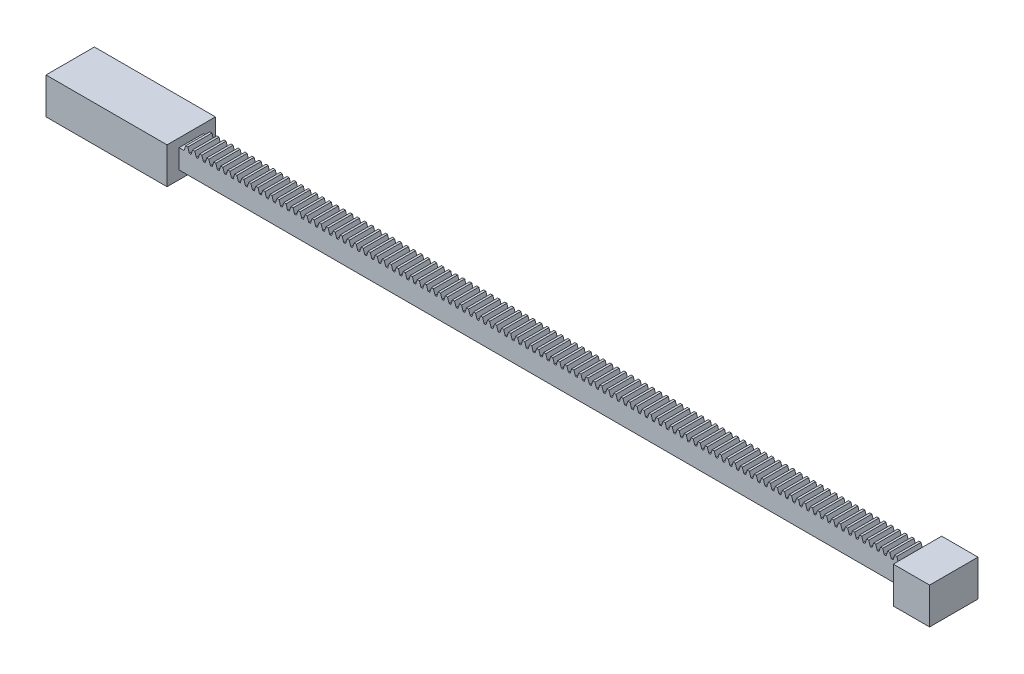
SolidWorks part; units mm, degrees
ref_plane "Front Plane" through (0, 0, 0) normal (0, 0, 1) x (1, 0, 0)
ref_plane "Top Plane" through (0, 0, 0) normal (0, 1, 0) x (1, 0, 0)
ref_plane "Right Plane" through (0, 0, 0) normal (1, 0, 0) x (0, 0, -1)
sketch "Sketch1" plane through (0, 0, 0) normal (0, 0, 1) x (1, 0, 0)
  line L0 (147.8394, 4) -> (148.4797, 6)
  line L1 (-150, 4) -> (150, 4)
  line L2 (-150, 4) -> (-150, -4)
  line L3 (-150, -4) -> (150, -4)
  line L4 (150, 4) -> (150, -4)
  line L5 (-150, 4) -> (150, -4) construction
  line L6 (-150, -4) -> (150, 4) construction
  line L7 (148.4797, 6) -> (149.3597, 6)
  line L8 (149.3597, 6) -> (150, 4)
  line L9 (144.9394, 4) -> (145.5797, 6)
  line L10 (145.5797, 6) -> (146.4597, 6)
  line L11 (146.4597, 6) -> (147.1, 4)
  line L12 (142.0394, 4) -> (142.6797, 6)
  line L13 (142.6797, 6) -> (143.5597, 6)
  line L14 (143.5597, 6) -> (144.2, 4)
  line L15 (139.1394, 4) -> (139.7797, 6)
  line L16 (139.7797, 6) -> (140.6597, 6)
  line L17 (140.6597, 6) -> (141.3, 4)
  line L18 (136.2394, 4) -> (136.8797, 6)
  line L19 (136.8797, 6) -> (137.7597, 6)
  line L20 (137.7597, 6) -> (138.4, 4)
  line L21 (133.3394, 4) -> (133.9797, 6)
  line L22 (133.9797, 6) -> (134.8597, 6)
  line L23 (134.8597, 6) -> (135.5, 4)
  line L24 (130.4394, 4) -> (131.0797, 6)
  line L25 (131.0797, 6) -> (131.9597, 6)
  line L26 (131.9597, 6) -> (132.6, 4)
  line L27 (127.5394, 4) -> (128.1797, 6)
  line L28 (128.1797, 6) -> (129.0597, 6)
  line L29 (129.0597, 6) -> (129.7, 4)
  line L30 (124.6394, 4) -> (125.2797, 6)
  line L31 (125.2797, 6) -> (126.1597, 6)
  line L32 (126.1597, 6) -> (126.8, 4)
  line L33 (121.7394, 4) -> (122.3797, 6)
  line L34 (122.3797, 6) -> (123.2597, 6)
  line L35 (123.2597, 6) -> (123.9, 4)
  line L36 (118.8394, 4) -> (119.4797, 6)
  line L37 (119.4797, 6) -> (120.3597, 6)
  line L38 (120.3597, 6) -> (121, 4)
  line L39 (115.9394, 4) -> (116.5797, 6)
  line L40 (116.5797, 6) -> (117.4597, 6)
  line L41 (117.4597, 6) -> (118.1, 4)
  line L42 (113.0394, 4) -> (113.6797, 6)
  line L43 (113.6797, 6) -> (114.5597, 6)
  line L44 (114.5597, 6) -> (115.2, 4)
  line L45 (110.1394, 4) -> (110.7797, 6)
  line L46 (110.7797, 6) -> (111.6597, 6)
  line L47 (111.6597, 6) -> (112.3, 4)
  line L48 (107.2394, 4) -> (107.8797, 6)
  line L49 (107.8797, 6) -> (108.7597, 6)
  line L50 (108.7597, 6) -> (109.4, 4)
  line L51 (104.3394, 4) -> (104.9797, 6)
  line L52 (104.9797, 6) -> (105.8597, 6)
  line L53 (105.8597, 6) -> (106.5, 4)
  line L54 (101.4394, 4) -> (102.0797, 6)
  line L55 (102.0797, 6) -> (102.9597, 6)
  line L56 (102.9597, 6) -> (103.6, 4)
  line L57 (98.5394, 4) -> (99.1797, 6)
  line L58 (99.1797, 6) -> (100.0597, 6)
  line L59 (100.0597, 6) -> (100.7, 4)
  line L60 (95.6394, 4) -> (96.2797, 6)
  line L61 (96.2797, 6) -> (97.1597, 6)
  line L62 (97.1597, 6) -> (97.8, 4)
  line L63 (92.7394, 4) -> (93.3797, 6)
  line L64 (93.3797, 6) -> (94.2597, 6)
  line L65 (94.2597, 6) -> (94.9, 4)
  line L66 (89.8394, 4) -> (90.4797, 6)
  line L67 (90.4797, 6) -> (91.3597, 6)
  line L68 (91.3597, 6) -> (92, 4)
  line L69 (86.9394, 4) -> (87.5797, 6)
  line L70 (87.5797, 6) -> (88.4597, 6)
  line L71 (88.4597, 6) -> (89.1, 4)
  line L72 (84.0394, 4) -> (84.6797, 6)
  line L73 (84.6797, 6) -> (85.5597, 6)
  line L74 (85.5597, 6) -> (86.2, 4)
  line L75 (81.1394, 4) -> (81.7797, 6)
  line L76 (81.7797, 6) -> (82.6597, 6)
  line L77 (82.6597, 6) -> (83.3, 4)
  line L78 (78.2394, 4) -> (78.8797, 6)
  line L79 (78.8797, 6) -> (79.7597, 6)
  line L80 (79.7597, 6) -> (80.4, 4)
  line L81 (75.3394, 4) -> (75.9797, 6)
  line L82 (75.9797, 6) -> (76.8597, 6)
  line L83 (76.8597, 6) -> (77.5, 4)
  line L84 (72.4394, 4) -> (73.0797, 6)
  line L85 (73.0797, 6) -> (73.9597, 6)
  line L86 (73.9597, 6) -> (74.6, 4)
  line L87 (69.5394, 4) -> (70.1797, 6)
  line L88 (70.1797, 6) -> (71.0597, 6)
  line L89 (71.0597, 6) -> (71.7, 4)
  line L90 (66.6394, 4) -> (67.2797, 6)
  line L91 (67.2797, 6) -> (68.1597, 6)
  line L92 (68.1597, 6) -> (68.8, 4)
  line L93 (63.7394, 4) -> (64.3797, 6)
  line L94 (64.3797, 6) -> (65.2597, 6)
  line L95 (65.2597, 6) -> (65.9, 4)
  line L96 (60.8394, 4) -> (61.4797, 6)
  line L97 (61.4797, 6) -> (62.3597, 6)
  line L98 (62.3597, 6) -> (63, 4)
  line L99 (57.9394, 4) -> (58.5797, 6)
  line L100 (58.5797, 6) -> (59.4597, 6)
  line L101 (59.4597, 6) -> (60.1, 4)
  line L102 (55.0394, 4) -> (55.6797, 6)
  line L103 (55.6797, 6) -> (56.5597, 6)
  line L104 (56.5597, 6) -> (57.2, 4)
  line L105 (52.1394, 4) -> (52.7797, 6)
  line L106 (52.7797, 6) -> (53.6597, 6)
  line L107 (53.6597, 6) -> (54.3, 4)
  line L108 (49.2394, 4) -> (49.8797, 6)
  line L109 (49.8797, 6) -> (50.7597, 6)
  line L110 (50.7597, 6) -> (51.4, 4)
  line L111 (46.3394, 4) -> (46.9797, 6)
  line L112 (46.9797, 6) -> (47.8597, 6)
  line L113 (47.8597, 6) -> (48.5, 4)
  line L114 (43.4394, 4) -> (44.0797, 6)
  line L115 (44.0797, 6) -> (44.9597, 6)
  line L116 (44.9597, 6) -> (45.6, 4)
  line L117 (40.5394, 4) -> (41.1797, 6)
  line L118 (41.1797, 6) -> (42.0597, 6)
  line L119 (42.0597, 6) -> (42.7, 4)
  line L120 (37.6394, 4) -> (38.2797, 6)
  line L121 (38.2797, 6) -> (39.1597, 6)
  line L122 (39.1597, 6) -> (39.8, 4)
  line L123 (34.7394, 4) -> (35.3797, 6)
  line L124 (35.3797, 6) -> (36.2597, 6)
  line L125 (36.2597, 6) -> (36.9, 4)
  line L126 (31.8394, 4) -> (32.4797, 6)
  line L127 (32.4797, 6) -> (33.3597, 6)
  line L128 (33.3597, 6) -> (34, 4)
  line L129 (28.9394, 4) -> (29.5797, 6)
  line L130 (29.5797, 6) -> (30.4597, 6)
  line L131 (30.4597, 6) -> (31.1, 4)
  line L132 (26.0394, 4) -> (26.6797, 6)
  line L133 (26.6797, 6) -> (27.5597, 6)
  line L134 (27.5597, 6) -> (28.2, 4)
  line L135 (23.1394, 4) -> (23.7797, 6)
  line L136 (23.7797, 6) -> (24.6597, 6)
  line L137 (24.6597, 6) -> (25.3, 4)
  line L138 (20.2394, 4) -> (20.8797, 6)
  line L139 (20.8797, 6) -> (21.7597, 6)
  line L140 (21.7597, 6) -> (22.4, 4)
  line L141 (17.3394, 4) -> (17.9797, 6)
  line L142 (17.9797, 6) -> (18.8597, 6)
  line L143 (18.8597, 6) -> (19.5, 4)
  line L144 (14.4394, 4) -> (15.0797, 6)
  line L145 (15.0797, 6) -> (15.9597, 6)
  line L146 (15.9597, 6) -> (16.6, 4)
  line L147 (11.5394, 4) -> (12.1797, 6)
  line L148 (12.1797, 6) -> (13.0597, 6)
  line L149 (13.0597, 6) -> (13.7, 4)
  line L150 (8.6394, 4) -> (9.2797, 6)
  line L151 (9.2797, 6) -> (10.1597, 6)
  line L152 (10.1597, 6) -> (10.8, 4)
  line L153 (5.7394, 4) -> (6.3797, 6)
  line L154 (6.3797, 6) -> (7.2597, 6)
  line L155 (7.2597, 6) -> (7.9, 4)
  line L156 (2.8394, 4) -> (3.4797, 6)
  line L157 (3.4797, 6) -> (4.3597, 6)
  line L158 (4.3597, 6) -> (5, 4)
  line L159 (-0.0606, 4) -> (0.5797, 6)
  line L160 (0.5797, 6) -> (1.4597, 6)
  line L161 (1.4597, 6) -> (2.1, 4)
  line L162 (-2.9606, 4) -> (-2.3203, 6)
  line L163 (-2.3203, 6) -> (-1.4403, 6)
  line L164 (-1.4403, 6) -> (-0.8, 4)
  line L165 (-5.8606, 4) -> (-5.2203, 6)
  line L166 (-5.2203, 6) -> (-4.3403, 6)
  line L167 (-4.3403, 6) -> (-3.7, 4)
  line L168 (-8.7606, 4) -> (-8.1203, 6)
  line L169 (-8.1203, 6) -> (-7.2403, 6)
  line L170 (-7.2403, 6) -> (-6.6, 4)
  line L171 (-11.6606, 4) -> (-11.0203, 6)
  line L172 (-11.0203, 6) -> (-10.1403, 6)
  line L173 (-10.1403, 6) -> (-9.5, 4)
  line L174 (-14.5606, 4) -> (-13.9203, 6)
  line L175 (-13.9203, 6) -> (-13.0403, 6)
  line L176 (-13.0403, 6) -> (-12.4, 4)
  line L177 (-17.4606, 4) -> (-16.8203, 6)
  line L178 (-16.8203, 6) -> (-15.9403, 6)
  line L179 (-15.9403, 6) -> (-15.3, 4)
  line L180 (-20.3606, 4) -> (-19.7203, 6)
  line L181 (-19.7203, 6) -> (-18.8403, 6)
  line L182 (-18.8403, 6) -> (-18.2, 4)
  line L183 (-23.2606, 4) -> (-22.6203, 6)
  line L184 (-22.6203, 6) -> (-21.7403, 6)
  line L185 (-21.7403, 6) -> (-21.1, 4)
  line L186 (-26.1606, 4) -> (-25.5203, 6)
  line L187 (-25.5203, 6) -> (-24.6403, 6)
  line L188 (-24.6403, 6) -> (-24, 4)
  line L189 (-29.0606, 4) -> (-28.4203, 6)
  line L190 (-28.4203, 6) -> (-27.5403, 6)
  line L191 (-27.5403, 6) -> (-26.9, 4)
  line L192 (-31.9606, 4) -> (-31.3203, 6)
  line L193 (-31.3203, 6) -> (-30.4403, 6)
  line L194 (-30.4403, 6) -> (-29.8, 4)
  line L195 (-34.8606, 4) -> (-34.2203, 6)
  line L196 (-34.2203, 6) -> (-33.3403, 6)
  line L197 (-33.3403, 6) -> (-32.7, 4)
  line L198 (-37.7606, 4) -> (-37.1203, 6)
  line L199 (-37.1203, 6) -> (-36.2403, 6)
  line L200 (-36.2403, 6) -> (-35.6, 4)
  line L201 (-40.6606, 4) -> (-40.0203, 6)
  line L202 (-40.0203, 6) -> (-39.1403, 6)
  line L203 (-39.1403, 6) -> (-38.5, 4)
  line L204 (-43.5606, 4) -> (-42.9203, 6)
  line L205 (-42.9203, 6) -> (-42.0403, 6)
  line L206 (-42.0403, 6) -> (-41.4, 4)
  line L207 (-46.4606, 4) -> (-45.8203, 6)
  line L208 (-45.8203, 6) -> (-44.9403, 6)
  line L209 (-44.9403, 6) -> (-44.3, 4)
  line L210 (-49.3606, 4) -> (-48.7203, 6)
  line L211 (-48.7203, 6) -> (-47.8403, 6)
  line L212 (-47.8403, 6) -> (-47.2, 4)
  line L213 (-52.2606, 4) -> (-51.6203, 6)
  line L214 (-51.6203, 6) -> (-50.7403, 6)
  line L215 (-50.7403, 6) -> (-50.1, 4)
  line L216 (-55.1606, 4) -> (-54.5203, 6)
  line L217 (-54.5203, 6) -> (-53.6403, 6)
  line L218 (-53.6403, 6) -> (-53, 4)
  line L219 (-58.0606, 4) -> (-57.4203, 6)
  line L220 (-57.4203, 6) -> (-56.5403, 6)
  line L221 (-56.5403, 6) -> (-55.9, 4)
  line L222 (-60.9606, 4) -> (-60.3203, 6)
  line L223 (-60.3203, 6) -> (-59.4403, 6)
  line L224 (-59.4403, 6) -> (-58.8, 4)
  line L225 (-63.8606, 4) -> (-63.2203, 6)
  line L226 (-63.2203, 6) -> (-62.3403, 6)
  line L227 (-62.3403, 6) -> (-61.7, 4)
  line L228 (-66.7606, 4) -> (-66.1203, 6)
  line L229 (-66.1203, 6) -> (-65.2403, 6)
  line L230 (-65.2403, 6) -> (-64.6, 4)
  line L231 (-69.6606, 4) -> (-69.0203, 6)
  line L232 (-69.0203, 6) -> (-68.1403, 6)
  line L233 (-68.1403, 6) -> (-67.5, 4)
  line L234 (-72.5606, 4) -> (-71.9203, 6)
  line L235 (-71.9203, 6) -> (-71.0403, 6)
  line L236 (-71.0403, 6) -> (-70.4, 4)
  line L237 (-75.4606, 4) -> (-74.8203, 6)
  line L238 (-74.8203, 6) -> (-73.9403, 6)
  line L239 (-73.9403, 6) -> (-73.3, 4)
  line L240 (-78.3606, 4) -> (-77.7203, 6)
  line L241 (-77.7203, 6) -> (-76.8403, 6)
  line L242 (-76.8403, 6) -> (-76.2, 4)
  line L243 (-81.2606, 4) -> (-80.6203, 6)
  line L244 (-80.6203, 6) -> (-79.7403, 6)
  line L245 (-79.7403, 6) -> (-79.1, 4)
  line L246 (-84.1606, 4) -> (-83.5203, 6)
  line L247 (-83.5203, 6) -> (-82.6403, 6)
  line L248 (-82.6403, 6) -> (-82, 4)
  line L249 (-87.0606, 4) -> (-86.4203, 6)
  line L250 (-86.4203, 6) -> (-85.5403, 6)
  line L251 (-85.5403, 6) -> (-84.9, 4)
  line L252 (-89.9606, 4) -> (-89.3203, 6)
  line L253 (-89.3203, 6) -> (-88.4403, 6)
  line L254 (-88.4403, 6) -> (-87.8, 4)
  line L255 (-92.8606, 4) -> (-92.2203, 6)
  line L256 (-92.2203, 6) -> (-91.3403, 6)
  line L257 (-91.3403, 6) -> (-90.7, 4)
  line L258 (-95.7606, 4) -> (-95.1203, 6)
  line L259 (-95.1203, 6) -> (-94.2403, 6)
  line L260 (-94.2403, 6) -> (-93.6, 4)
  line L261 (-98.6606, 4) -> (-98.0203, 6)
  line L262 (-98.0203, 6) -> (-97.1403, 6)
  line L263 (-97.1403, 6) -> (-96.5, 4)
  line L264 (-101.5606, 4) -> (-100.9203, 6)
  line L265 (-100.9203, 6) -> (-100.0403, 6)
  line L266 (-100.0403, 6) -> (-99.4, 4)
  line L267 (-104.4606, 4) -> (-103.8203, 6)
  line L268 (-103.8203, 6) -> (-102.9403, 6)
  line L269 (-102.9403, 6) -> (-102.3, 4)
  line L270 (-107.3606, 4) -> (-106.7203, 6)
  line L271 (-106.7203, 6) -> (-105.8403, 6)
  line L272 (-105.8403, 6) -> (-105.2, 4)
  line L273 (-110.2606, 4) -> (-109.6203, 6)
  line L274 (-109.6203, 6) -> (-108.7403, 6)
  line L275 (-108.7403, 6) -> (-108.1, 4)
  line L276 (-113.1606, 4) -> (-112.5203, 6)
  line L277 (-112.5203, 6) -> (-111.6403, 6)
  line L278 (-111.6403, 6) -> (-111, 4)
  line L279 (-116.0606, 4) -> (-115.4203, 6)
  line L280 (-115.4203, 6) -> (-114.5403, 6)
  line L281 (-114.5403, 6) -> (-113.9, 4)
  line L282 (-118.9606, 4) -> (-118.3203, 6)
  line L283 (-118.3203, 6) -> (-117.4403, 6)
  line L284 (-117.4403, 6) -> (-116.8, 4)
  line L285 (-121.8606, 4) -> (-121.2203, 6)
  line L286 (-121.2203, 6) -> (-120.3403, 6)
  line L287 (-120.3403, 6) -> (-119.7, 4)
  line L288 (-124.7606, 4) -> (-124.1203, 6)
  line L289 (-124.1203, 6) -> (-123.2403, 6)
  line L290 (-123.2403, 6) -> (-122.6, 4)
  line L291 (-127.6606, 4) -> (-127.0203, 6)
  line L292 (-127.0203, 6) -> (-126.1403, 6)
  line L293 (-126.1403, 6) -> (-125.5, 4)
  line L294 (-130.5606, 4) -> (-129.9203, 6)
  line L295 (-129.9203, 6) -> (-129.0403, 6)
  line L296 (-129.0403, 6) -> (-128.4, 4)
  line L297 (-133.4606, 4) -> (-132.8203, 6)
  line L298 (-132.8203, 6) -> (-131.9403, 6)
  line L299 (-131.9403, 6) -> (-131.3, 4)
  line L300 (-136.3606, 4) -> (-135.7203, 6)
  line L301 (-135.7203, 6) -> (-134.8403, 6)
  line L302 (-134.8403, 6) -> (-134.2, 4)
  line L303 (-139.2606, 4) -> (-138.6203, 6)
  line L304 (-138.6203, 6) -> (-137.7403, 6)
  line L305 (-137.7403, 6) -> (-137.1, 4)
  line L306 (-142.1606, 4) -> (-141.5203, 6)
  line L307 (-141.5203, 6) -> (-140.6403, 6)
  line L308 (-140.6403, 6) -> (-140, 4)
  line L309 (-145.0606, 4) -> (-144.4203, 6)
  line L310 (-144.4203, 6) -> (-143.5403, 6)
  line L311 (-143.5403, 6) -> (-142.9, 4)
  line L312 (-147.9606, 4) -> (-147.3203, 6)
  line L313 (-147.3203, 6) -> (-146.4403, 6)
  line L314 (-146.4403, 6) -> (-145.8, 4)
  point P0 (0, 0)
  dimension "D1" = 8
  dimension "D2" = 300
  dimension "D3" = 0.88
  dimension "D4" = 2
  dimension "D5" = 2.1
  dimension "D6" = 2.1606
  dimension "D7" = 103
extrude "Boss-Extrude1" add sketch "Sketch1" along normal blind 10 contours L4 L1 region at (0, 0, 0)
sketch "Sketch2" plane through (0, 0, 10) normal (0, 0, 1) x (1, 0, 0)
  line L3 (147.8394, 4) -> (148.4797, 6)
  line L4 (150, -4) -> (150, 4)
  line L5 (150, 4) -> (-150, 4)
  line L6 (-150, 4) -> (-150, -4)
  line L7 (-150, -4) -> (150, -4)
  line L9 (150, 4) -> (147.8394, 4)
  line L12 (148.4797, 6) -> (149.3597, 6)
  line L13 (149.3597, 6) -> (150, 4)
  dimension "D1" = 0
extrude "Boss-Extrude2" add sketch "Sketch2" against normal blind 10
pattern_linear "LPattern1" count 103 spacing 2.9 along (-1, 0, 0) of "Boss-Extrude2"
sketch "Sketch3" plane through (150, 0, 0) normal (1, 0, 0) x (0, 0, -1)
  line L0 (-10, -4) -> (0, -4) construction
  line L1 (-15, 7.5) -> (5, 7.5)
  line L2 (-15, 7.5) -> (-15, -7.5)
  line L3 (-15, -7.5) -> (5, -7.5)
  line L4 (5, 7.5) -> (5, -7.5)
  line L5 (-15, 7.5) -> (5, -7.5) construction
  line L6 (-15, -7.5) -> (5, 7.5) construction
  point P0 (-5, 0)
  point P5 (0, 0)
  point P8 (-5, -4)
  dimension "D1" = 20
  dimension "D2" = 15
extrude "Boss-Extrude3" add sketch "Sketch3" along normal blind 15
sketch "Sketch4" plane through (-150, 0, 0) normal (-1, 0, 0) x (0, 0, 1)
  line L0 (-5, -7.5) -> (-5, 7.5) construction
  line L1 (-5, -7.5) -> (-5, 7.5)
  line L2 (15, -7.5) -> (-5, -7.5) construction
  line L3 (15, 7.5) -> (15, -7.5) construction
  line L4 (-5, 7.5) -> (15, 7.5) construction
  line L5 (15, -7.5) -> (-5, -7.5)
  line L6 (15, 7.5) -> (15, -7.5)
  line L7 (-5, 7.5) -> (15, 7.5)
extrude "Boss-Extrude4" add sketch "Sketch4" along normal blind 50
